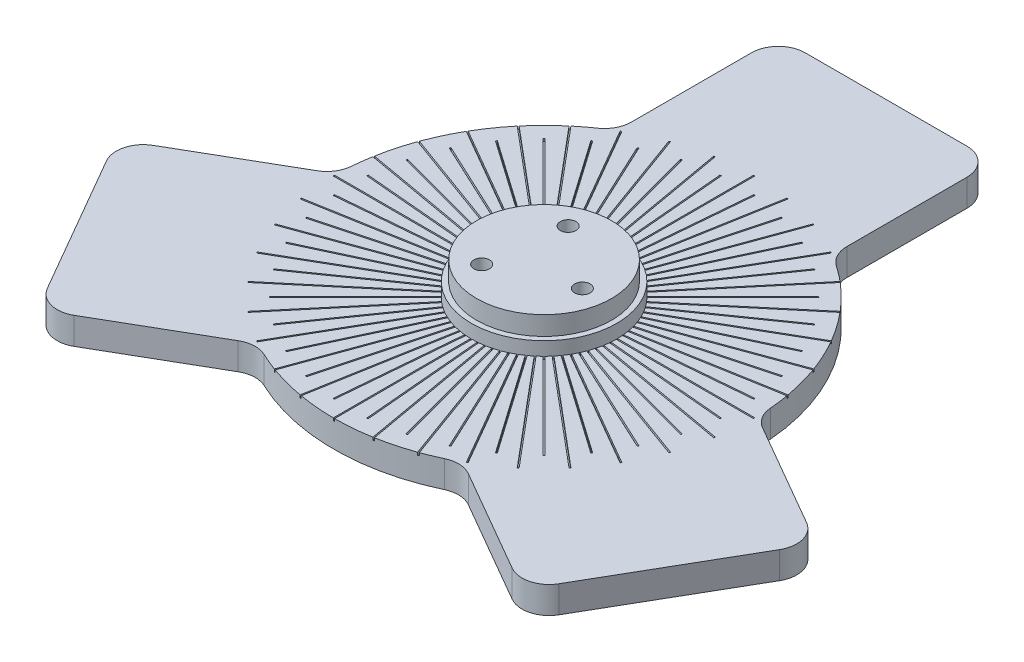
SolidWorks part; units mm, degrees
ref_plane "Front Plane" through (0, 0, 0) normal (0, 0, 1) x (1, 0, 0)
ref_plane "Top Plane" through (0, 0, 0) normal (0, 1, 0) x (1, 0, 0)
ref_plane "Right Plane" through (0, 0, 0) normal (1, 0, 0) x (0, 0, -1)
sketch "Sketch1" plane through (0, 0, 0) normal (0, 1, 0) x (1, 0, 0)
  line L0 (-40, 66.9627) -> (-40, 126.9627)
  line L1 (-40, 126.9627) -> (40, 126.9627)
  line L2 (40, 126.9627) -> (40, 66.9627)
  line L3 (89.9529, -98.1224) -> (37.9914, -68.1224)
  line L4 (129.9529, -28.8403) -> (89.9529, -98.1224)
  line L5 (77.9914, 1.1597) -> (129.9529, -28.8403)
  line L6 (-129.9529, -28.8403) -> (-77.9914, 1.1597)
  line L7 (-89.9529, -98.1224) -> (-129.9529, -28.8403)
  line L8 (-37.9914, -68.1224) -> (-89.9529, -98.1224)
  circle A0 centre (0, 0) radius 78
  arc A1 (-40, 66.9627) -> (40, 66.9627) centre (0, 0) cw
  arc A2 (77.9914, 1.1597) -> (37.9914, -68.1224) centre (0, 0) cw
  arc A3 (-37.9914, -68.1224) -> (-77.9914, 1.1597) centre (0, 0) cw
  point P5 (0, 126.9627)
  point P20 (0, 0)
  dimension "D1" = 156
  dimension "D2" = 80
  dimension "D3" = 60
  dimension "D4" = 3
extrude "Boss-Extrude1" add sketch "Sketch1" along normal blind 10 contours A0 L2 L1 L0 | A0 | L6 A3 L8 L7 | L3 A2 L5 L4 region at (0, 0, -100.5965) region at (0, 0, 0)
sketch "Sketch2" plane through (0, 10, 0) normal (0, 1, 0) x (1, 0, 0)
  circle A0 centre (0, 0) radius 27
  dimension "D1" = 54
extrude "Boss-Extrude2" add sketch "Sketch2" along normal blind 5
sketch "Sketch3" plane through (0, 15, 0) normal (0, 1, 0) x (1, 0, 0)
  circle A0 centre (0, 0) radius 25.05
  dimension "D1" = 50.1
extrude "Boss-Extrude3" add sketch "Sketch3" along normal blind 7
sketch "Sketch6" plane through (0, 0, 0) normal (0, -1, 0) x (-1, 0, 0)
  line L0 (6.3181, 15.2533) -> (0, 0) construction
  line L1 (0, 0) -> (10.0507, -13.0983) construction
  line L3 (0, 0) -> (-16.3688, -2.155) construction
  line L4 (0, 0) -> (0, -64.4806) construction
  point P0 (-16.3688, -2.155)
  point P2 (6.3181, 15.2533)
  point P4 (10.0507, -13.0983)
  dimension "D1" = 16.51
  dimension "D2" = 82.5
  dimension "D3" = 120
  dimension "D4" = 120
hole_wizard "CBORE for M5 SHCS1" positions "Sketch6" profile "Sketch5" counterbore size "M5" standard "ANSI Metric" end condition through all
sketch "Sketch5" plane through (16.3688, 0, 2.155) normal (1, 0, 0) x (0, 0, -1)
  line L0 (0, 0) -> (0, 22)
  line L1 (0, 22) -> (2.9, 22)
  line L3 (2.9, 22) -> (2.9, 5)
  line L4 (5, 5) -> (2.9, 5)
  line L5 (5, 5) -> (5, 0.025)
  line L6 (5, 0.025) -> (5.025, 0)
  line L7 (5.025, 0) -> (0, 0)
  line L8 (-5, 0.025) -> (-5.025, 0) construction
  line L11 (0, -6.35) -> (0, 107.95) construction
  dimension "Thru Hole Dia." = 5.8
  dimension "Thru Hole Depth" = 22
  dimension "C'Bore Dia." = 10
  dimension "C'Bore Depth" = 5
  dimension "Near C'Sink Dia." = 10.05
  dimension "Near C'Sink Angle" = 90
fillet "Fillet1" radius 10 12 edges at (40, 5, -66.9627) (-40, 5, -66.9627) (40, 5, -126.9627) (-40, 5, -126.9627) (77.9914, 5, -1.1597) (129.9529, 5, 28.8403) (89.9529, 5, 98.1224) (37.9914, 5, 68.1224) (-37.9914, 5, 68.1224) (-89.9529, 5, 98.1224) (-129.9529, 5, 28.8403) (-77.9914, 5, -1.1597)
ref_axis "Axis1" through (0, 102.4683, 0) along (0, -1, 0)
sketch "Sketch7" plane through (0, 10, 0) normal (0, 1, 0) x (1, 0, 0)
  line L0 (13.2984, 76.8584) -> (4.4423, 26.6332)
  line L1 (-0.25, 78) -> (0.25, 78)
  line L2 (-0.25, 78) -> (-0.25, 27)
  line L3 (-0.25, 27) -> (0.25, 27)
  line L4 (0.25, 78) -> (0.25, 27)
  line L5 (13.2984, 76.8584) -> (13.7908, 76.7716)
  line L6 (13.7908, 76.7716) -> (4.9347, 26.5464)
  line L7 (4.4423, 26.6332) -> (4.9347, 26.5464)
  line L8 (26.4426, 73.3815) -> (8.9996, 25.4572)
  line L9 (26.4426, 73.3815) -> (26.9125, 73.2105)
  line L10 (26.9125, 73.2105) -> (9.4695, 25.2862)
  line L11 (8.9996, 25.4572) -> (9.4695, 25.2862)
  line L12 (38.7835, 67.675) -> (13.2835, 23.5077)
  line L13 (38.7835, 67.675) -> (39.2165, 67.425)
  line L14 (39.2165, 67.425) -> (13.7165, 23.2577)
  line L15 (13.2835, 23.5077) -> (13.7165, 23.2577)
  line L16 (49.9459, 59.9122) -> (17.1638, 20.8439)
  line L17 (49.9459, 59.9122) -> (50.3289, 59.5908)
  line L18 (50.3289, 59.5908) -> (17.5468, 20.5225)
  line L19 (17.1638, 20.8439) -> (17.5468, 20.5225)
  line L20 (59.5908, 50.3289) -> (20.5225, 17.5468)
  line L21 (59.5908, 50.3289) -> (59.9122, 49.9459)
  line L22 (59.9122, 49.9459) -> (20.8439, 17.1638)
  line L23 (20.5225, 17.5468) -> (20.8439, 17.1638)
  line L24 (67.425, 39.2165) -> (23.2577, 13.7165)
  line L25 (67.425, 39.2165) -> (67.675, 38.7835)
  line L26 (67.675, 38.7835) -> (23.5077, 13.2835)
  line L27 (23.2577, 13.7165) -> (23.5077, 13.2835)
  line L28 (73.2105, 26.9125) -> (25.2862, 9.4695)
  line L29 (73.2105, 26.9125) -> (73.3815, 26.4426)
  line L30 (73.3815, 26.4426) -> (25.4572, 8.9996)
  line L31 (25.2862, 9.4695) -> (25.4572, 8.9996)
  line L32 (76.7716, 13.7908) -> (26.5464, 4.9347)
  line L33 (76.7716, 13.7908) -> (76.8584, 13.2984)
  line L34 (76.8584, 13.2984) -> (26.6332, 4.4423)
  line L35 (26.5464, 4.9347) -> (26.6332, 4.4423)
  line L36 (78, 0.25) -> (27, 0.25)
  line L37 (78, 0.25) -> (78, -0.25)
  line L38 (78, -0.25) -> (27, -0.25)
  line L39 (27, 0.25) -> (27, -0.25)
  line L40 (76.8584, -13.2984) -> (26.6332, -4.4423)
  line L41 (76.8584, -13.2984) -> (76.7716, -13.7908)
  line L42 (76.7716, -13.7908) -> (26.5464, -4.9347)
  line L43 (26.6332, -4.4423) -> (26.5464, -4.9347)
  line L44 (73.3815, -26.4426) -> (25.4572, -8.9996)
  line L45 (73.3815, -26.4426) -> (73.2105, -26.9125)
  line L46 (73.2105, -26.9125) -> (25.2862, -9.4695)
  line L47 (25.4572, -8.9996) -> (25.2862, -9.4695)
  line L48 (67.675, -38.7835) -> (23.5077, -13.2835)
  line L49 (67.675, -38.7835) -> (67.425, -39.2165)
  line L50 (67.425, -39.2165) -> (23.2577, -13.7165)
  line L51 (23.5077, -13.2835) -> (23.2577, -13.7165)
  line L52 (59.9122, -49.9459) -> (20.8439, -17.1638)
  line L53 (59.9122, -49.9459) -> (59.5908, -50.3289)
  line L54 (59.5908, -50.3289) -> (20.5225, -17.5468)
  line L55 (20.8439, -17.1638) -> (20.5225, -17.5468)
  line L56 (50.3289, -59.5908) -> (17.5468, -20.5225)
  line L57 (50.3289, -59.5908) -> (49.9459, -59.9122)
  line L58 (49.9459, -59.9122) -> (17.1638, -20.8439)
  line L59 (17.5468, -20.5225) -> (17.1638, -20.8439)
  line L60 (39.2165, -67.425) -> (13.7165, -23.2577)
  line L61 (39.2165, -67.425) -> (38.7835, -67.675)
  line L62 (38.7835, -67.675) -> (13.2835, -23.5077)
  line L63 (13.7165, -23.2577) -> (13.2835, -23.5077)
  line L64 (26.9125, -73.2105) -> (9.4695, -25.2862)
  line L65 (26.9125, -73.2105) -> (26.4426, -73.3815)
  line L66 (26.4426, -73.3815) -> (8.9996, -25.4572)
  line L67 (9.4695, -25.2862) -> (8.9996, -25.4572)
  line L68 (13.7908, -76.7716) -> (4.9347, -26.5464)
  line L69 (13.7908, -76.7716) -> (13.2984, -76.8584)
  line L70 (13.2984, -76.8584) -> (4.4423, -26.6332)
  line L71 (4.9347, -26.5464) -> (4.4423, -26.6332)
  line L72 (0.25, -78) -> (0.25, -27)
  line L73 (0.25, -78) -> (-0.25, -78)
  line L74 (-0.25, -78) -> (-0.25, -27)
  line L75 (0.25, -27) -> (-0.25, -27)
  line L76 (-13.2984, -76.8584) -> (-4.4423, -26.6332)
  line L77 (-13.2984, -76.8584) -> (-13.7908, -76.7716)
  line L78 (-13.7908, -76.7716) -> (-4.9347, -26.5464)
  line L79 (-4.4423, -26.6332) -> (-4.9347, -26.5464)
  line L80 (-26.4426, -73.3815) -> (-8.9996, -25.4572)
  line L81 (-26.4426, -73.3815) -> (-26.9125, -73.2105)
  line L82 (-26.9125, -73.2105) -> (-9.4695, -25.2862)
  line L83 (-8.9996, -25.4572) -> (-9.4695, -25.2862)
  line L84 (-38.7835, -67.675) -> (-13.2835, -23.5077)
  line L85 (-38.7835, -67.675) -> (-39.2165, -67.425)
  line L86 (-39.2165, -67.425) -> (-13.7165, -23.2577)
  line L87 (-13.2835, -23.5077) -> (-13.7165, -23.2577)
  line L88 (-49.9459, -59.9122) -> (-17.1638, -20.8439)
  line L89 (-49.9459, -59.9122) -> (-50.3289, -59.5908)
  line L90 (-50.3289, -59.5908) -> (-17.5468, -20.5225)
  line L91 (-17.1638, -20.8439) -> (-17.5468, -20.5225)
  line L92 (-59.5908, -50.3289) -> (-20.5225, -17.5468)
  line L93 (-59.5908, -50.3289) -> (-59.9122, -49.9459)
  line L94 (-59.9122, -49.9459) -> (-20.8439, -17.1638)
  line L95 (-20.5225, -17.5468) -> (-20.8439, -17.1638)
  line L96 (-67.425, -39.2165) -> (-23.2577, -13.7165)
  line L97 (-67.425, -39.2165) -> (-67.675, -38.7835)
  line L98 (-67.675, -38.7835) -> (-23.5077, -13.2835)
  line L99 (-23.2577, -13.7165) -> (-23.5077, -13.2835)
  line L100 (-73.2105, -26.9125) -> (-25.2862, -9.4695)
  line L101 (-73.2105, -26.9125) -> (-73.3815, -26.4426)
  line L102 (-73.3815, -26.4426) -> (-25.4572, -8.9996)
  line L103 (-25.2862, -9.4695) -> (-25.4572, -8.9996)
  line L104 (-76.7716, -13.7908) -> (-26.5464, -4.9347)
  line L105 (-76.7716, -13.7908) -> (-76.8584, -13.2984)
  line L106 (-76.8584, -13.2984) -> (-26.6332, -4.4423)
  line L107 (-26.5464, -4.9347) -> (-26.6332, -4.4423)
  line L108 (-78, -0.25) -> (-27, -0.25)
  line L109 (-78, -0.25) -> (-78, 0.25)
  line L110 (-78, 0.25) -> (-27, 0.25)
  line L111 (-27, -0.25) -> (-27, 0.25)
  line L112 (-76.8584, 13.2984) -> (-26.6332, 4.4423)
  line L113 (-76.8584, 13.2984) -> (-76.7716, 13.7908)
  line L114 (-76.7716, 13.7908) -> (-26.5464, 4.9347)
  line L115 (-26.6332, 4.4423) -> (-26.5464, 4.9347)
  line L116 (-73.3815, 26.4426) -> (-25.4572, 8.9996)
  line L117 (-73.3815, 26.4426) -> (-73.2105, 26.9125)
  line L118 (-73.2105, 26.9125) -> (-25.2862, 9.4695)
  line L119 (-25.4572, 8.9996) -> (-25.2862, 9.4695)
  line L120 (-67.675, 38.7835) -> (-23.5077, 13.2835)
  line L121 (-67.675, 38.7835) -> (-67.425, 39.2165)
  line L122 (-67.425, 39.2165) -> (-23.2577, 13.7165)
  line L123 (-23.5077, 13.2835) -> (-23.2577, 13.7165)
  line L124 (-59.9122, 49.9459) -> (-20.8439, 17.1638)
  line L125 (-59.9122, 49.9459) -> (-59.5908, 50.3289)
  line L126 (-59.5908, 50.3289) -> (-20.5225, 17.5468)
  line L127 (-20.8439, 17.1638) -> (-20.5225, 17.5468)
  line L128 (-50.3289, 59.5908) -> (-17.5468, 20.5225)
  line L129 (-50.3289, 59.5908) -> (-49.9459, 59.9122)
  line L130 (-49.9459, 59.9122) -> (-17.1638, 20.8439)
  line L131 (-17.5468, 20.5225) -> (-17.1638, 20.8439)
  line L132 (-39.2165, 67.425) -> (-13.7165, 23.2577)
  line L133 (-39.2165, 67.425) -> (-38.7835, 67.675)
  line L134 (-38.7835, 67.675) -> (-13.2835, 23.5077)
  line L135 (-13.7165, 23.2577) -> (-13.2835, 23.5077)
  line L136 (-26.9125, 73.2105) -> (-9.4695, 25.2862)
  line L137 (-26.9125, 73.2105) -> (-26.4426, 73.3815)
  line L138 (-26.4426, 73.3815) -> (-8.9996, 25.4572)
  line L139 (-9.4695, 25.2862) -> (-8.9996, 25.4572)
  line L140 (-13.7908, 76.7716) -> (-4.9347, 26.5464)
  line L141 (-13.7908, 76.7716) -> (-13.2984, 76.8584)
  line L142 (-13.2984, 76.8584) -> (-4.4423, 26.6332)
  line L143 (-4.9347, 26.5464) -> (-4.4423, 26.6332)
  circle A2 centre (0, 0) radius 27 construction
  arc A3 (-44.3182, 64.1864) -> (-77.7462, 6.2875) centre (0, 0) ccw construction
  point P4 (0, 27)
  point P153 (0, 0)
  dimension "D1" = 0.5
  dimension "D2" = 36
extrude "Cut-Extrude2" cut sketch "Sketch7" against normal blind 1
sketch "Sketch8" plane through (0, 10, 0) normal (0, 1, 0) x (1, 0, 0)
  line L0 (2.1112, 27) -> (6.0332, 71.8288)
  line L1 (6.0332, 71.8288) -> (6.5352, 71.8288)
  line L2 (6.5352, 71.8288) -> (2.6131, 27)
  line L3 (2.6131, 27) -> (2.1112, 27)
  line L4 (0, 27) -> (0, 78) construction
  line L5 (-0.25, 27) -> (0.25, 27) construction
  line L6 (0.25, 78) -> (-0.25, 78) construction
  line L7 (6.2842, 71.8288) -> (2.3622, 27) construction
  line L9 (7.262, 26.136) -> (6.7677, 26.2232)
  line L10 (6.7677, 26.2232) -> (18.4145, 69.6899)
  line L11 (18.4145, 69.6899) -> (18.9088, 69.6027)
  line L12 (18.9088, 69.6027) -> (7.262, 26.136)
  line L13 (11.6901, 24.478) -> (11.2185, 24.6496)
  line L14 (11.2185, 24.6496) -> (30.2363, 65.4335)
  line L15 (30.2363, 65.4335) -> (30.7079, 65.2618)
  line L16 (30.7079, 65.2618) -> (11.6901, 24.478)
  line L17 (15.7631, 22.0761) -> (15.3284, 22.3271)
  line L18 (15.3284, 22.3271) -> (41.1393, 59.1889)
  line L19 (41.1393, 59.1889) -> (41.574, 58.938)
  line L20 (41.574, 58.938) -> (15.7631, 22.0761)
  line L21 (19.3571, 19.0035) -> (18.9726, 19.3261)
  line L22 (18.9726, 19.3261) -> (50.7924, 51.1459)
  line L23 (50.7924, 51.1459) -> (51.1769, 50.8233)
  line L24 (51.1769, 50.8233) -> (19.3571, 19.0035)
  line L25 (22.3629, 15.3535) -> (22.0403, 15.738)
  line L26 (22.0403, 15.738) -> (58.9021, 41.5489)
  line L27 (58.9021, 41.5489) -> (59.2247, 41.1644)
  line L28 (59.2247, 41.1644) -> (22.3629, 15.3535)
  line L29 (24.6893, 11.2369) -> (24.4383, 11.6716)
  line L30 (24.4383, 11.6716) -> (65.2222, 30.6894)
  line L31 (65.2222, 30.6894) -> (65.4731, 30.2548)
  line L32 (65.4731, 30.2548) -> (24.6893, 11.2369)
  line L33 (26.2655, 6.779) -> (26.0938, 7.2506)
  line L34 (26.0938, 7.2506) -> (69.5604, 18.8975)
  line L35 (69.5604, 18.8975) -> (69.7321, 18.4258)
  line L36 (69.7321, 18.4258) -> (26.2655, 6.779)
  line L37 (27.0436, 2.1151) -> (26.9564, 2.6093)
  line L38 (26.9564, 2.6093) -> (71.7852, 6.5313)
  line L39 (71.7852, 6.5313) -> (71.8723, 6.0371)
  line L40 (71.8723, 6.0371) -> (27.0436, 2.1151)
  line L41 (27, -2.6131) -> (27, -2.1112)
  line L42 (27, -2.1112) -> (71.8288, -6.0332)
  line L43 (71.8288, -6.0332) -> (71.8288, -6.5352)
  line L44 (71.8288, -6.5352) -> (27, -2.6131)
  line L45 (26.136, -7.262) -> (26.2232, -6.7677)
  line L46 (26.2232, -6.7677) -> (69.6899, -18.4145)
  line L47 (69.6899, -18.4145) -> (69.6027, -18.9088)
  line L48 (69.6027, -18.9088) -> (26.136, -7.262)
  line L49 (24.478, -11.6901) -> (24.6496, -11.2185)
  line L50 (24.6496, -11.2185) -> (65.4335, -30.2363)
  line L51 (65.4335, -30.2363) -> (65.2618, -30.7079)
  line L52 (65.2618, -30.7079) -> (24.478, -11.6901)
  line L53 (22.0761, -15.7631) -> (22.3271, -15.3284)
  line L54 (22.3271, -15.3284) -> (59.1889, -41.1393)
  line L55 (59.1889, -41.1393) -> (58.938, -41.574)
  line L56 (58.938, -41.574) -> (22.0761, -15.7631)
  line L57 (19.0035, -19.3571) -> (19.3261, -18.9726)
  line L58 (19.3261, -18.9726) -> (51.1459, -50.7924)
  line L59 (51.1459, -50.7924) -> (50.8233, -51.1769)
  line L60 (50.8233, -51.1769) -> (19.0035, -19.3571)
  line L61 (15.3535, -22.3629) -> (15.738, -22.0403)
  line L62 (15.738, -22.0403) -> (41.5489, -58.9021)
  line L63 (41.5489, -58.9021) -> (41.1644, -59.2247)
  line L64 (41.1644, -59.2247) -> (15.3535, -22.3629)
  line L65 (11.2369, -24.6893) -> (11.6716, -24.4383)
  line L66 (11.6716, -24.4383) -> (30.6894, -65.2222)
  line L67 (30.6894, -65.2222) -> (30.2548, -65.4731)
  line L68 (30.2548, -65.4731) -> (11.2369, -24.6893)
  line L69 (6.779, -26.2655) -> (7.2506, -26.0938)
  line L70 (7.2506, -26.0938) -> (18.8975, -69.5604)
  line L71 (18.8975, -69.5604) -> (18.4258, -69.7321)
  line L72 (18.4258, -69.7321) -> (6.779, -26.2655)
  line L73 (2.1151, -27.0436) -> (2.6093, -26.9564)
  line L74 (2.6093, -26.9564) -> (6.5313, -71.7852)
  line L75 (6.5313, -71.7852) -> (6.0371, -71.8723)
  line L76 (6.0371, -71.8723) -> (2.1151, -27.0436)
  line L77 (-2.6131, -27) -> (-2.1112, -27)
  line L78 (-2.1112, -27) -> (-6.0332, -71.8288)
  line L79 (-6.0332, -71.8288) -> (-6.5352, -71.8288)
  line L80 (-6.5352, -71.8288) -> (-2.6131, -27)
  line L81 (-7.262, -26.136) -> (-6.7677, -26.2232)
  line L82 (-6.7677, -26.2232) -> (-18.4145, -69.6899)
  line L83 (-18.4145, -69.6899) -> (-18.9088, -69.6027)
  line L84 (-18.9088, -69.6027) -> (-7.262, -26.136)
  line L85 (-11.6901, -24.478) -> (-11.2185, -24.6496)
  line L86 (-11.2185, -24.6496) -> (-30.2363, -65.4335)
  line L87 (-30.2363, -65.4335) -> (-30.7079, -65.2618)
  line L88 (-30.7079, -65.2618) -> (-11.6901, -24.478)
  line L89 (-15.7631, -22.0761) -> (-15.3284, -22.3271)
  line L90 (-15.3284, -22.3271) -> (-41.1393, -59.1889)
  line L91 (-41.1393, -59.1889) -> (-41.574, -58.938)
  line L92 (-41.574, -58.938) -> (-15.7631, -22.0761)
  line L93 (-19.3571, -19.0035) -> (-18.9726, -19.3261)
  line L94 (-18.9726, -19.3261) -> (-50.7924, -51.1459)
  line L95 (-50.7924, -51.1459) -> (-51.1769, -50.8233)
  line L96 (-51.1769, -50.8233) -> (-19.3571, -19.0035)
  line L97 (-22.3629, -15.3535) -> (-22.0403, -15.738)
  line L98 (-22.0403, -15.738) -> (-58.9021, -41.5489)
  line L99 (-58.9021, -41.5489) -> (-59.2247, -41.1644)
  line L100 (-59.2247, -41.1644) -> (-22.3629, -15.3535)
  line L101 (-24.6893, -11.2369) -> (-24.4383, -11.6716)
  line L102 (-24.4383, -11.6716) -> (-65.2222, -30.6894)
  line L103 (-65.2222, -30.6894) -> (-65.4731, -30.2548)
  line L104 (-65.4731, -30.2548) -> (-24.6893, -11.2369)
  line L105 (-26.2655, -6.779) -> (-26.0938, -7.2506)
  line L106 (-26.0938, -7.2506) -> (-69.5604, -18.8975)
  line L107 (-69.5604, -18.8975) -> (-69.7321, -18.4258)
  line L108 (-69.7321, -18.4258) -> (-26.2655, -6.779)
  line L109 (-27.0436, -2.1151) -> (-26.9564, -2.6093)
  line L110 (-26.9564, -2.6093) -> (-71.7852, -6.5313)
  line L111 (-71.7852, -6.5313) -> (-71.8723, -6.0371)
  line L112 (-71.8723, -6.0371) -> (-27.0436, -2.1151)
  line L113 (-27, 2.6131) -> (-27, 2.1112)
  line L114 (-27, 2.1112) -> (-71.8288, 6.0332)
  line L115 (-71.8288, 6.0332) -> (-71.8288, 6.5352)
  line L116 (-71.8288, 6.5352) -> (-27, 2.6131)
  line L117 (-26.136, 7.262) -> (-26.2232, 6.7677)
  line L118 (-26.2232, 6.7677) -> (-69.6899, 18.4145)
  line L119 (-69.6899, 18.4145) -> (-69.6027, 18.9088)
  line L120 (-69.6027, 18.9088) -> (-26.136, 7.262)
  line L121 (-24.478, 11.6901) -> (-24.6496, 11.2185)
  line L122 (-24.6496, 11.2185) -> (-65.4335, 30.2363)
  line L123 (-65.4335, 30.2363) -> (-65.2618, 30.7079)
  line L124 (-65.2618, 30.7079) -> (-24.478, 11.6901)
  line L125 (-22.0761, 15.7631) -> (-22.3271, 15.3284)
  line L126 (-22.3271, 15.3284) -> (-59.1889, 41.1393)
  line L127 (-59.1889, 41.1393) -> (-58.938, 41.574)
  line L128 (-58.938, 41.574) -> (-22.0761, 15.7631)
  line L129 (-19.0035, 19.3571) -> (-19.3261, 18.9726)
  line L130 (-19.3261, 18.9726) -> (-51.1459, 50.7924)
  line L131 (-51.1459, 50.7924) -> (-50.8233, 51.1769)
  line L132 (-50.8233, 51.1769) -> (-19.0035, 19.3571)
  line L133 (-15.3535, 22.3629) -> (-15.738, 22.0403)
  line L134 (-15.738, 22.0403) -> (-41.5489, 58.9021)
  line L135 (-41.5489, 58.9021) -> (-41.1644, 59.2247)
  line L136 (-41.1644, 59.2247) -> (-15.3535, 22.3629)
  line L137 (-11.2369, 24.6893) -> (-11.6716, 24.4383)
  line L138 (-11.6716, 24.4383) -> (-30.6894, 65.2222)
  line L139 (-30.6894, 65.2222) -> (-30.2548, 65.4731)
  line L140 (-30.2548, 65.4731) -> (-11.2369, 24.6893)
  line L141 (-6.779, 26.2655) -> (-7.2506, 26.0938)
  line L142 (-7.2506, 26.0938) -> (-18.8975, 69.5604)
  line L143 (-18.8975, 69.5604) -> (-18.4258, 69.7321)
  line L144 (-18.4258, 69.7321) -> (-6.779, 26.2655)
  line L145 (-2.1151, 27.0436) -> (-2.6093, 26.9564)
  line L146 (-2.6093, 26.9564) -> (-6.5313, 71.7852)
  line L147 (-6.5313, 71.7852) -> (-6.0371, 71.8723)
  line L148 (-6.0371, 71.8723) -> (-2.1151, 27.0436)
  arc A1 (4.6885, 26.5898) -> (0, 27) centre (0, 0) ccw construction
  point P159 (0, 0)
  dimension "D1" = 0.5
  dimension "D2" = 5
  dimension "D3" = 45
  dimension "D4" = 36
extrude "Cut-Extrude3" cut sketch "Sketch8" against normal blind 1
